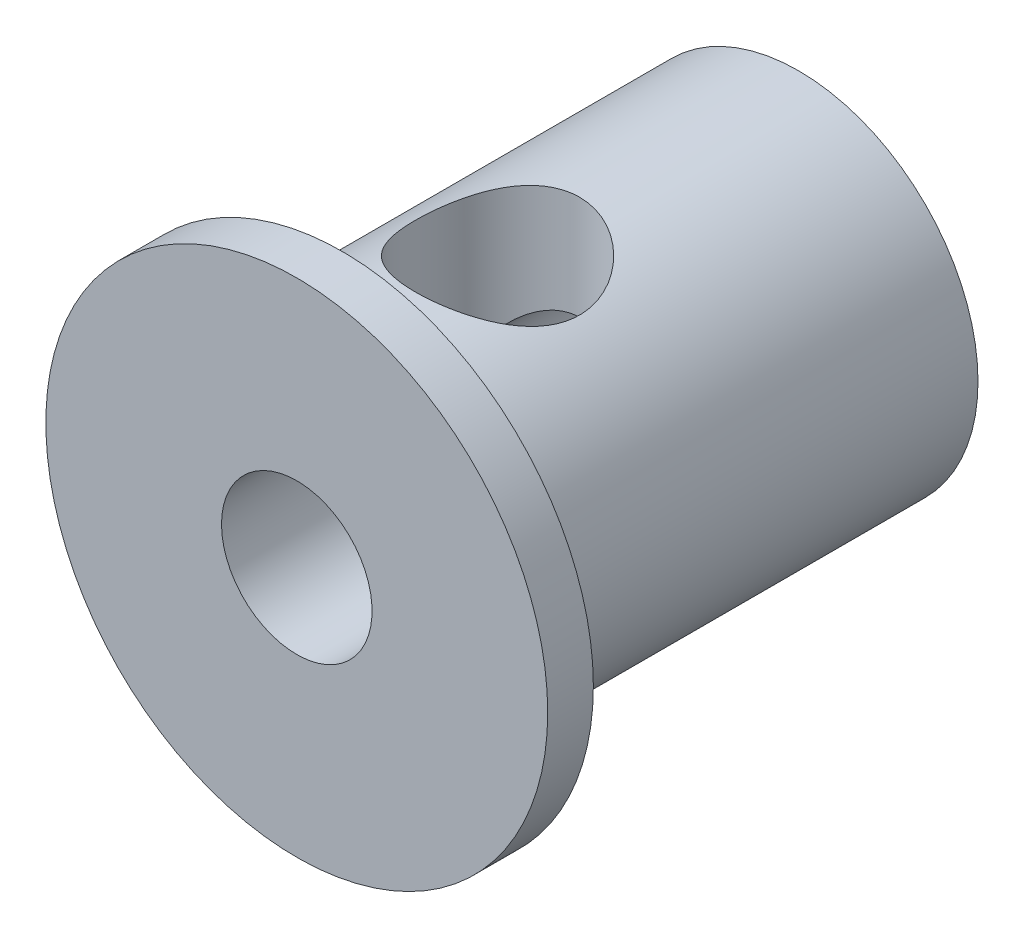
SolidWorks part; units mm, degrees
material "PLA2"
ref_plane "Front Plane" through (0, 0, 0) normal (0, 0, 1) x (1, 0, 0)
ref_plane "Top Plane" through (0, 0, 0) normal (0, 1, 0) x (1, 0, 0)
ref_plane "Right Plane" through (0, 0, 0) normal (1, 0, 0) x (0, 0, -1)
sketch "Sketch2" plane through (0, 0, 0) normal (0, 0, 1) x (1, 0, 0)
  circle A1 centre (0, 0) radius 4.9911
  circle A2 centre (0, 0) radius 2.0955
  dimension "D1" = 4.191
  dimension "D3" = 9.9822
extrude "Boss-Extrude1" add sketch "Sketch2" along normal blind 12.7
sketch "Sketch3" plane through (0, 0, 0) normal (0, -1, 0) x (1, 0, 0)
  line L0 (0, 8.382) -> (0, 0) construction
  line L1 (-4.9911, 6.35) -> (4.9911, 6.35) construction
  line L2 (-4.9911, 12.7) -> (-4.9911, 0) construction
  line L3 (4.9911, 0) -> (4.9911, 12.7) construction
  line L4 (4.9911, 12.7) -> (-4.9911, 12.7) construction
  circle A0 centre (0, 8.382) radius 2.286
  dimension "D1" = 4.572
  dimension "D2" = 4.318
extrude "Cut-Extrude1" cut sketch "Sketch3" against normal mid plane 25.4
sketch "Sketch4" plane through (0, 0, 0) normal (1, 0, 0) x (0, 0, -1)
  line L1 (0, 0) -> (50000, 0) construction
  line L2 (-12.7, 0) -> (-12.7, 6.985)
  line L3 (-12.7, 6.985) -> (-13.97, 6.985)
  line L4 (-13.97, 6.985) -> (-13.97, 0)
  line L5 (-13.97, 0) -> (-12.7, 0)
  line L6 (-12.7, 4.9911) -> (-12.7, -4.9911) construction
  dimension "D1" = 1.27
  dimension "D2" = 13.97
revolve "Revolve1" add sketch "Sketch4" angle 360 about L1
fillet "Fillet1" radius 0.381 1 edges at (4.9911, 0, 12.7)
sketch "Sketch5" plane through (0, 0, 12.7) normal (0, 0, -1) x (-1, 0, 0)
  circle A1 centre (0, 0) radius 2.0955
  circle A2 centre (0, 0) radius 2.0955
  dimension "D1" = 0
extrude "Cut-Extrude2" cut sketch "Sketch5" against normal through all
